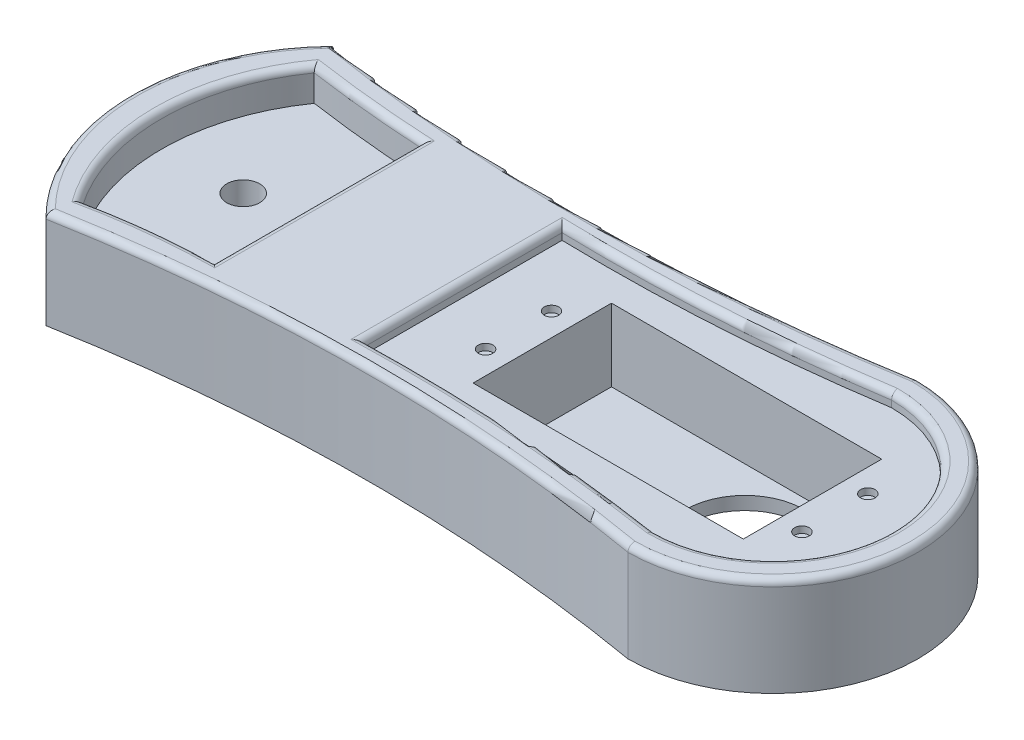
SolidWorks part; units mm, degrees
ref_plane "Alzado" through (0, 0, 0) normal (0, 0, 1) x (1, 0, 0)
ref_plane "Planta" through (0, 0, 0) normal (0, 1, 0) x (1, 0, 0)
ref_plane "Vista lateral" through (0, 0, 0) normal (1, 0, 0) x (0, 0, -1)
sketch "Croquis1" plane through (0, 0, 0) normal (0, 1, 0) x (1, 0, 0)
  arc A0 (0, -22) -> (0, 22) centre (0, 0) ccw
  arc A1 (-87.9325, -22.3651) -> (-88.2978, 21.6334) centre (-66.1159, -0.1832) cw
  arc A2 (-88.2978, 21.6334) -> (0, 22) centre (-45.249, 286.8045) ccw
  arc A3 (-87.9325, -22.3651) -> (0, -22) centre (-42.9311, -271.5275) cw
  dimension "D1" = 44
extrude "Saliente-Extruir1" add sketch "Croquis1" along normal blind 15
sketch "Croquis2" plane through (0, 15, 0) normal (0, 1, 0) x (1, 0, 0)
  line L0 (-64.7022, 0) -> (27.9658, 0) construction
  line L1 (-47, 15) -> (-47, -15)
  arc A0 (0, -18) -> (0, 18) centre (0, 0) ccw
  arc A1 (0, -22) -> (0, 22) centre (0, 0) ccw construction
  arc A2 (-47, -15) -> (0, -18) centre (-40.2458, -278.8507) cw
  arc A5 (-47, 15) -> (0, 18) centre (-40.4155, 281.5101) ccw
  dimension "D1" = 36
extrude "Cortar-Extruir2" cut sketch "Croquis2" against normal blind 2
sketch "Croquis3" plane through (0, 13, 0) normal (0, 1, 0) x (1, 0, 0)
  line L0 (-47, 15) -> (-47, -15) construction
  line L1 (-35, 10.5) -> (6, 10.5)
  line L2 (-35, 10.5) -> (-35, -10.5)
  line L3 (-35, -10.5) -> (6, -10.5)
  line L4 (6, 10.5) -> (6, -10.5)
  line L5 (-14.5, -10.5) -> (-14.5, 10.5) construction
  point P11 (-14.5, 10.5)
  dimension "D3" = 0
  dimension "D1" = 41
  dimension "D2" = 12
extrude "Cortar-Extruir3" cut sketch "Croquis3" against normal blind 11
sketch "Croquis4" plane through (0, 2, 0) normal (0, 1, 0) x (1, 0, 0)
  circle A0 centre (-4.25, 0) radius 9
  dimension "D1" = 18
extrude "Cortar-Extruir4" cut sketch "Croquis4" against normal through all
sketch "Croquis5" plane through (0, 13, 0) normal (0, 1, 0) x (1, 0, 0)
  circle A0 centre (9.5, 4.9) radius 1.1
  circle A1 centre (9.5, -5.1) radius 1.1
  circle A2 centre (-38.5, 4.9) radius 1.1
  circle A3 centre (-38.5, -5.1) radius 1.1
extrude "Cortar-Extruir5" cut sketch "Croquis5" against normal blind 1
sketch "Croquis6" plane through (0, 15, 0) normal (0, 1, 0) x (1, 0, 0)
  line L0 (-68.7377, 15.4271) -> (-68.7377, -15.9735)
  line L3 (-103.7065, -0.2596) -> (-48.1182, -0.2596) construction
  line L4 (-80.5548, 28.9001) -> (-80.5548, -29.7074) construction
  line L13 (-92.3718, 32.6334) -> (-92.3718, -36.0982) construction
  arc A0 (-86.7985, 17.1989) -> (-86.7985, -18.011) centre (-61.7875, -0.406) ccw
  arc A1 (-86.7985, 17.1989) -> (-68.7377, 15.4271) centre (-58.1217, 216.5727) ccw
  arc A2 (-86.7985, -18.011) -> (-68.7377, -15.9735) centre (-66.6706, -115.3634) cw
  circle A3 centre (-80.5548, -0.4036) radius 2.5
extrude "Cortar-Extruir13" cut sketch "Croquis6" against normal blind 5 contours A0 A2 L0 A1
sketch "Croquis7" plane through (0, 10, 0) normal (0, 1, 0) x (1, 0, 0)
  circle A0 centre (-80.3733, 0) radius 2.5
extrude "Cortar-Extruir14" cut sketch "Croquis7" against normal through all
sketch "Croquis8" plane through (0, 12, 0) normal (0, 1, 0) x (1, 0, 0)
fillet "Redondeo2" radius 1 4 edges at (-43.9822, 15, 18.336) (22, 15, 0) (-44.1338, 15, -18.1641) (-97.2276, 15, 0.4415)
fillet "Redondeo3" radius 1 8 edges at (-77.8148, 15, 16.5786) (-92.3732, 15, 0.406) (-77.7881, 15, -16.1095) (-68.7377, 15, 0.2732) (-23.433, 15, 15.4496) (-47, 15, 0) (-23.4336, 15, -15.4601) (18, 15, 0)
